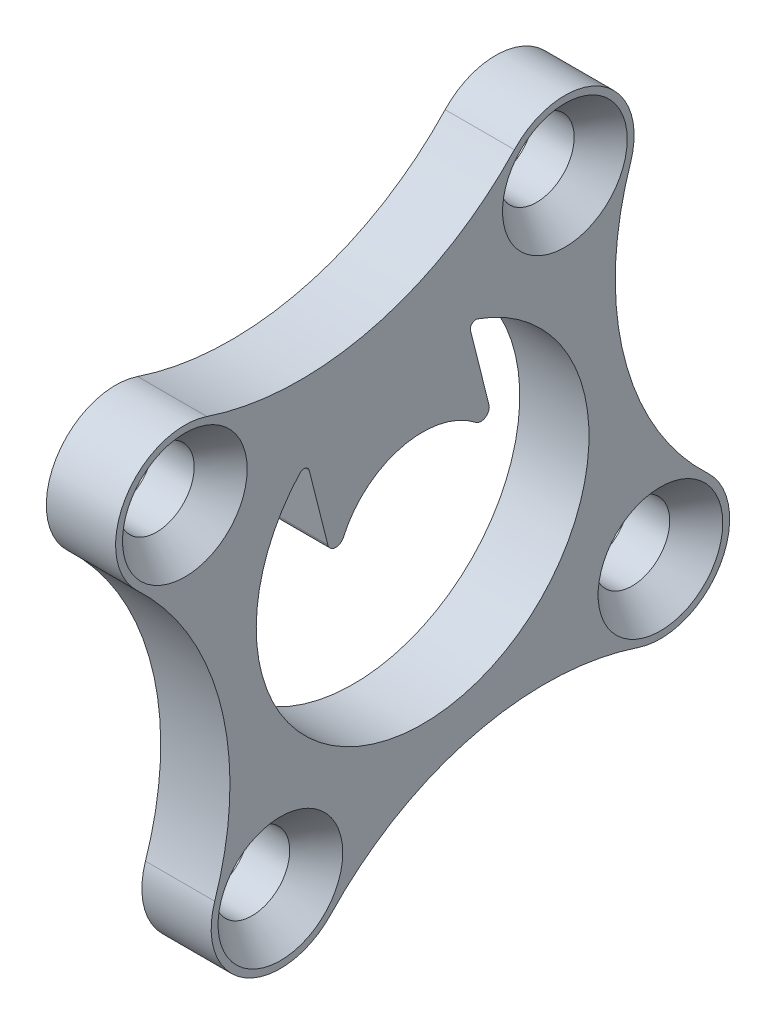
SolidWorks part; units mm, degrees
material "6061-T6 (SS)"
ref_plane "Front Plane" through (0, 0, 0) normal (0, 0, 1) x (1, 0, 0)
ref_plane "Top Plane" through (0, 0, 0) normal (0, 1, 0) x (1, 0, 0)
ref_plane "Right Plane" through (0, 0, 0) normal (1, 0, 0) x (0, 0, -1)
sketch "Sketch1" plane through (-42.315, 0, 0) normal (-1, 0, 0) x (0, 0, 1)
  line L0 (5.1951, 5.0371) -> (4.3476, 1.6664)
  line L1 (5.6075, 6.6773) -> (5.1578, 4.8889) construction
  line L2 (-3.0424, 3.5245) -> (-2.1949, 6.8952)
  line L3 (-1.7825, 8.5354) -> (-2.9982, 3.7003) construction
  line L5 (5.1578, 4.8889) -> (3.966, 0.1487) construction
  line L6 (6.5194, -10.8989) -> (-6.5194, 10.8989) construction
  line L7 (-10.8989, -6.5194) -> (10.8989, 6.5194) construction
  arc A0 (4.3476, 1.6664) -> (3.6296, 1.6052) centre (3.9781, 1.7593) cw
  arc A1 (3.6296, 1.6052) -> (-2.4388, 3.131) centre (0, 0) ccw
  arc A2 (-2.4388, 3.131) -> (-3.0424, 3.5245) centre (-2.6729, 3.4316) cw
  circle A3 centre (0, 0) radius 3.9687 construction
  circle A4 centre (0, 0) radius 3.9687 construction
  arc A5 (5.1951, 5.0371) -> (5.6289, 5.1466) centre (5.4414, 4.9752) cw
  arc A8 (5.6289, 5.1466) -> (-2.5254, 7.1968) centre (0, 0) cw
  arc A9 (-2.5254, 7.1968) -> (-2.1949, 6.8952) centre (-2.4413, 6.9571) cw
  circle A10 centre (0, 0) radius 15.875
  arc A11 (-2.5654, 7.0476) -> (5.5936, 4.9962) centre (0, 0) ccw construction
  circle A12 centre (10.8989, 6.5194) radius 3.175 construction
  circle A13 centre (10.8989, 6.5194) radius 2.6924 construction
  circle A14 centre (0, 0) radius 9.525 construction
  dimension "D1" = 0.381
  dimension "D2" = 0.254
  dimension "D3" = 25.4
  dimension "D4" = 0.127
  dimension "D6" = 5.3848
  dimension "D7" = 19.05
  dimension "D5" = 45
extrude "Boss-Extrude1" add sketch "Sketch1" against normal blind 3.175
sketch "Sketch2" plane through (-42.315, 0, 0) normal (-1, 0, 0) x (0, 0, 1)
  line L0 (-10.8989, -6.5194) -> (10.8989, 6.5194) construction
  line L1 (5.1951, 5.0371) -> (4.3476, 1.6664) construction
  line L2 (9.2375, -2.3226) -> (15.3958, -3.871)
  arc A0 (13.6237, 8.1493) -> (15.3958, -3.871) centre (0, 0) cw
  circle A1 centre (0, 0) radius 15.875 construction
  circle A3 centre (0, 0) radius 9.525 construction
  arc A5 (13.0739, 4.2063) -> (13.6237, 8.1493) centre (10.8989, 6.5194) ccw
  circle A6 centre (10.8989, 6.5194) radius 3.175 construction
  arc A7 (13.0739, 4.2063) -> (9.2375, -2.3226) centre (22.3013, -5.6072) ccw
extrude "Cut-Extrude1" cut sketch "Sketch2" against normal through all
mirror "Mirror1" about plane through (-39.14, -2.3226, 9.2375) normal (0, -0.9698, -0.2438) of "Cut-Extrude1"
pattern_circular "CirPattern2" count 4 over 360 about axis through (-42.315, 0, 0) along (-1, 0, 0) of "Cut-Extrude1", "Mirror1"
hole_wizard "CSK for #4 Flat Head Machine Screw1" positions "Sketch3" profile "Sketch4" countersink size "#4" standard "ANSI Inch" end condition up to next
sketch "Sketch3" plane through (-39.14, 0, 0) normal (1, 0, 0) x (0, 0, -1)
  point P0 (6.5194, 10.8989)
  point P3 (6.5194, 10.8989)
  point P6 (6.5194, 10.8989)
  point P9 (6.5194, 10.8989)
  point P13 (-10.8989, 6.5194)
  point P16 (-6.5194, -10.8989)
  point P19 (10.8989, -6.5194)
sketch "Sketch4" plane through (-39.14, 10.8989, -6.5194) normal (0, 1, 0) x (0, 0, -1)
  line L0 (0, 0) -> (0, 3.175)
  line L1 (0, 3.175) -> (1.7272, 3.175)
  line L2 (1.7272, 3.175) -> (1.7272, 1.3003)
  line L3 (1.7272, 1.3003) -> (2.8575, 0)
  line L5 (2.8575, 0) -> (0, 0)
  line L6 (-1.7272, 1.3003) -> (-2.8575, 0) construction
  line L11 (0, -6.35) -> (0, 107.95) construction
  dimension "Thru Hole Dia." = 3.4544
  dimension "Thru Hole Depth" = 3.175
  dimension "Near C'Sink Dia." = 5.715
  dimension "Near C'Sink Angle" = 82
